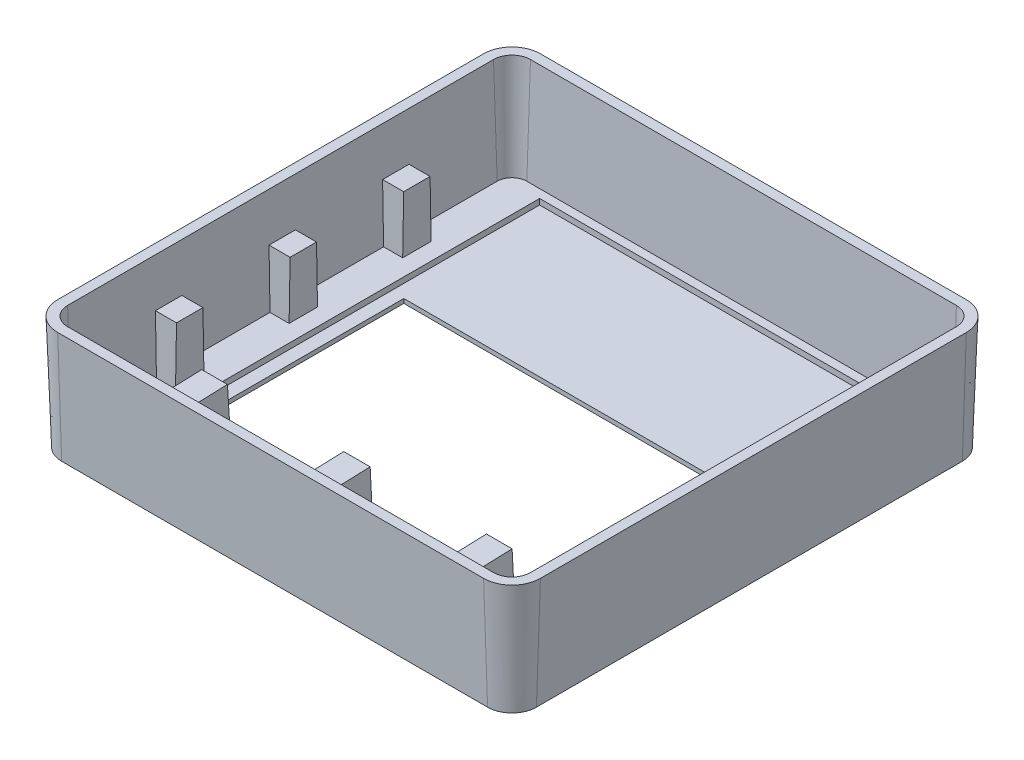
SolidWorks part; units mm, degrees
material "ABS"
ref_plane "Front Plane" through (0, 0, 0) normal (0, 0, 1) x (1, 0, 0)
ref_plane "Top Plane" through (0, 0, 0) normal (0, 1, 0) x (1, 0, 0)
ref_plane "Right Plane" through (0, 0, 0) normal (1, 0, 0) x (0, 0, -1)
sketch "Sketch1" plane through (0, 0, 0) normal (0, 1, 0) x (1, 0, 0)
  line L1 (-7.5, -8.5) -> (7.5, -8.5)
  line L2 (-8.5, -7.5) -> (-8.5, 7.5)
  line L3 (-7.5, 8.5) -> (7.5, 8.5)
  line L4 (8.5, -7.5) -> (8.5, 7.5)
  line L5 (-8.5, -8.5) -> (8.5, 8.5) construction
  line L6 (-8.5, 8.5) -> (8.5, -8.5) construction
  arc A0 (-8.5, 7.5) -> (-7.5, 8.5) centre (-7.5, 7.5) cw
  arc A1 (8.5, 7.5) -> (7.5, 8.5) centre (7.5, 7.5) ccw
  arc A2 (8.5, -7.5) -> (7.5, -8.5) centre (7.5, -7.5) cw
  arc A3 (-7.5, -8.5) -> (-8.5, -7.5) centre (-7.5, -7.5) cw
  point P0 (0, 0)
  dimension "D3" = 1
  dimension "D1" = 17
  dimension "D2" = 17
extrude "Boss-Extrude1" add sketch "Sketch1" against normal blind 4 draft 2
shell "Shell1" thickness 0.35 removed face at (0, 0, 0)
sketch "Sketch2" plane through (0, -4, 0) normal (0, -1, 0) x (1, 0, 0)
  line L0 (-7.5, 8.5) -> (7.5, 8.5) construction
  line L1 (-6.29, 4.5) -> (6.29, 4.5)
  line L2 (-6.29, 4.5) -> (-6.29, -2.48)
  line L3 (-6.29, -2.48) -> (6.29, -2.48)
  line L4 (6.29, 4.5) -> (6.29, -2.48)
  point P0 (0, 0)
  dimension "D1" = 4
  dimension "D2" = 6.98
extrude "Cut-Extrude1" cut sketch "Sketch2" against normal blind 2
sketch "Sketch3" plane through (0, -3.65, 0) normal (0, 1, 0) x (1, 0, 0)
  line L1 (6.75, 7.7223) -> (-6.75, 7.7223)
  line L2 (6.75, 7.7223) -> (6.75, -5.31)
  line L3 (6.75, -5.31) -> (-6.75, -5.31)
  line L4 (-6.75, 7.7223) -> (-6.75, -5.31)
  line L5 (6.29, 2.48) -> (6.29, -4.5) construction
  line L6 (-6.29, -4.5) -> (-6.29, 2.48) construction
  line L8 (6.29, -4.5) -> (-6.29, -4.5) construction
  line L9 (7.5, 8.0223) -> (-7.5, 8.0223) construction
  point P0 (0, 0)
  dimension "D1" = 0.81
  dimension "D2" = 0.46
  dimension "D3" = 0.46
  dimension "D4" = 0.3
extrude "Cut-Extrude2" cut sketch "Sketch3" against normal blind 0.2
ref_plane "Plane1" through (0, -1.65, 0) normal (0, -1, 0) x (-1, 0, 0)
ref_plane "Plane3" through (0, -0.1925, 5.5115) normal (0, 0.0349, -0.9994) x (-1, 0, 0)
sketch "Sketch10" plane through (0, -0.1925, 5.5115) normal (0, 0.0349, -0.9994) x (-1, 0, 0)
  line L0 (-0.5, -3.4457) -> (-0.4387, -1.4442)
  line L1 (0.5, -3.4457) -> (0.4651, -1.4442)
  line L2 (-0.4387, -1.4442) -> (0.4651, -1.4442)
  line L4 (-0.5, -3.4457) -> (0.5, -3.4457)
  dimension "D2" = 1
extrude "Boss-Extrude2" add sketch "Sketch10" against normal up to surface (2.63 mm away) up to face at (0, -1.825, 8.0861)
ref_plane "Plane4" through (7.35, 0, 0) normal (-1, 0, 0) x (0, 0, 1)
sketch "Sketch11" plane through (7.35, 0, 0) normal (-1, 0, 0) x (0, 0, 1)
  line L1 (-0.4651, -1.65) -> (0.4651, -1.65)
  line L3 (-0.5, -3.65) -> (0.5, -3.65)
  line L5 (-7.5, -3.65) -> (7.5, -3.65) construction
  line L7 (0.5, -3.65) -> (0.4651, -1.65)
  line L8 (-0.5, -3.65) -> (-0.4651, -1.65)
extrude "Boss-Extrude3" add sketch "Sketch11" against normal up to surface (0.6723 mm away) up to face at (8.0861, -1.825, 0)
ref_plane "Plane5" through (-7.35, 0, 0) normal (1, 0, 0) x (0, 0, -1)
sketch "Sketch13" plane through (-7.35, 0, 0) normal (1, 0, 0) x (0, 0, -1)
  line L3 (-0.5, -3.65) -> (0.5, -3.65)
  line L6 (0.5, -3.65) -> (0.4651, -1.65)
  line L7 (-0.5, -3.65) -> (-0.4651, -1.65)
  line L8 (-0.4651, -1.65) -> (0.4651, -1.65)
extrude "Boss-Extrude4" add sketch "Sketch13" against normal up to surface (0.6723 mm away) up to face at (-8.0861, -1.825, 0)
ref_plane "Plane6" through (0, 0, 0) normal (1, 0, 0.0016) x (0.0016, 0, -1)
pattern_linear "LPattern1" count 2 spacing 5 along (-1, 0, 0) of "Boss-Extrude2"
mirror "Mirror3" about plane through (0, 0, 0) normal (1, 0, 0) of "LPattern1"
pattern_linear "LPattern2" count 2 spacing 4 along (0, 0, 1) of "Boss-Extrude3"
mirror "Mirror4" about plane through (0, 0, 0) normal (0, 0, 1) of "LPattern2"
pattern_linear "LPattern3" count 2 spacing 4 along (0, 0, 1) of "Boss-Extrude4"
mirror "Mirror5" about plane through (0, 0, 0) normal (0, 0, 1) of "LPattern3"
